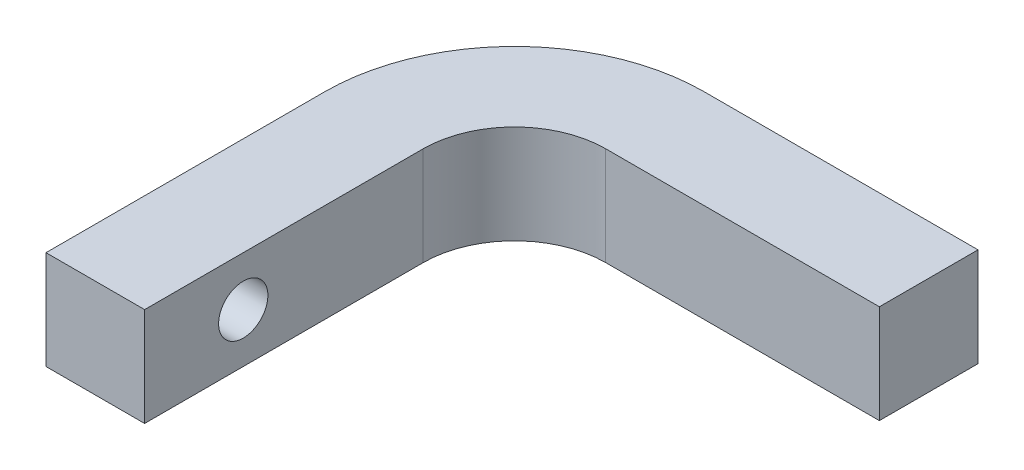
SolidWorks part; units mm, degrees
ref_plane "Front Plane" through (0, 0, 0) normal (0, 0, 1) x (1, 0, 0)
ref_plane "Top Plane" through (0, 0, 0) normal (0, 1, 0) x (1, 0, 0)
ref_plane "Right Plane" through (0, 0, 0) normal (1, 0, 0) x (0, 0, -1)
ref_axis "Z" through (0, 0, -1.9) along (0, 0, 1)
sketch "Sketch1" plane through (0, 0, 0) normal (0, 1, 0) x (1, 0, 0)
  line L0 (-11.1, 0) -> (11.1, 0)
  line L1 (-26.5, -15.4) -> (-26.5, -38)
  line L2 (-26.5, -38) -> (-18.5, -38)
  line L3 (-18.5, -38) -> (-18.5, -15.4)
  line L4 (-11.1, -8) -> (11.1, -8)
  line L5 (0, -8) -> (0, 0) construction
  line L6 (18.5, -38) -> (18.5, -15.4) construction
  line L7 (26.5, -38) -> (18.5, -38) construction
  line L8 (26.5, -15.4) -> (26.5, -38) construction
  line L9 (11.1, 0) -> (11.1, -8)
  arc A0 (-11.1, 0) -> (-26.5, -15.4) centre (-11.1, -15.4) ccw
  arc A1 (-18.5, -15.4) -> (-11.1, -8) centre (-11.1, -15.4) cw
  arc A2 (18.5, -15.4) -> (11.1, -8) centre (11.1, -15.4) ccw construction
  arc A3 (11.1, 0) -> (26.5, -15.4) centre (11.1, -15.4) cw construction
  dimension "D3" = 7.4
  dimension "D1" = 37
  dimension "D2" = 8
  dimension "D4" = 30
extrude "Boss-Extrude1" add sketch "Sketch1" along normal blind 4 and the other way blind 4
sketch "Sketch2" plane through (-18.5, 0, 0) normal (-1, 0, 0) x (0, 0, 1)
  line L1 (55, 0) -> (-55, 0) construction
  line L2 (0, -55) -> (0, 55) construction
  circle A0 centre (30, 0) radius 2
  dimension "D1" = 4
  dimension "D2" = 30
extrude "Cut-Extrude1" cut sketch "Sketch2" against normal through all both and the other way through all
ref_axis "Axis2" through (-60.1767, 0, 30) along (1, 0, 0)
equation "\"width\"= \"EyeDiameter\" + \"EyeClearance\""
equation "\"prongwidth\"= 8"
equation "\"D2@Sketch1\"=\"prongwidth\""
equation "\"D3@Sketch1\"=\"width\"/5"
equation "\"pronglength\"= \"BasePlaneDistance\"'model implicitly adds clearance (of prongwidth) to the hole drilled at the baseplanedistance"
equation "\"D4@Sketch1\"=\"pronglength\""
equation "\"D1@Boss-Extrude1\"=\"prongwidth\"/2"
equation "\"D2@Boss-Extrude1\"=\"prongwidth\"/2"
equation "\"lbracket-plane-to-axis\"= \"BasePlaneDistance\""
equation "\"D2@Sketch2\"=\"lbracket-plane-to-axis\""
equation "\"EyeDiameter\" = 35"
equation "\"BasePlaneDistance\" = 30"
equation "\"EyeClearance\" = 2"
equation "\"D1@Sketch1\"=\"EyeDiameter\"+\"EyeClearance\""
